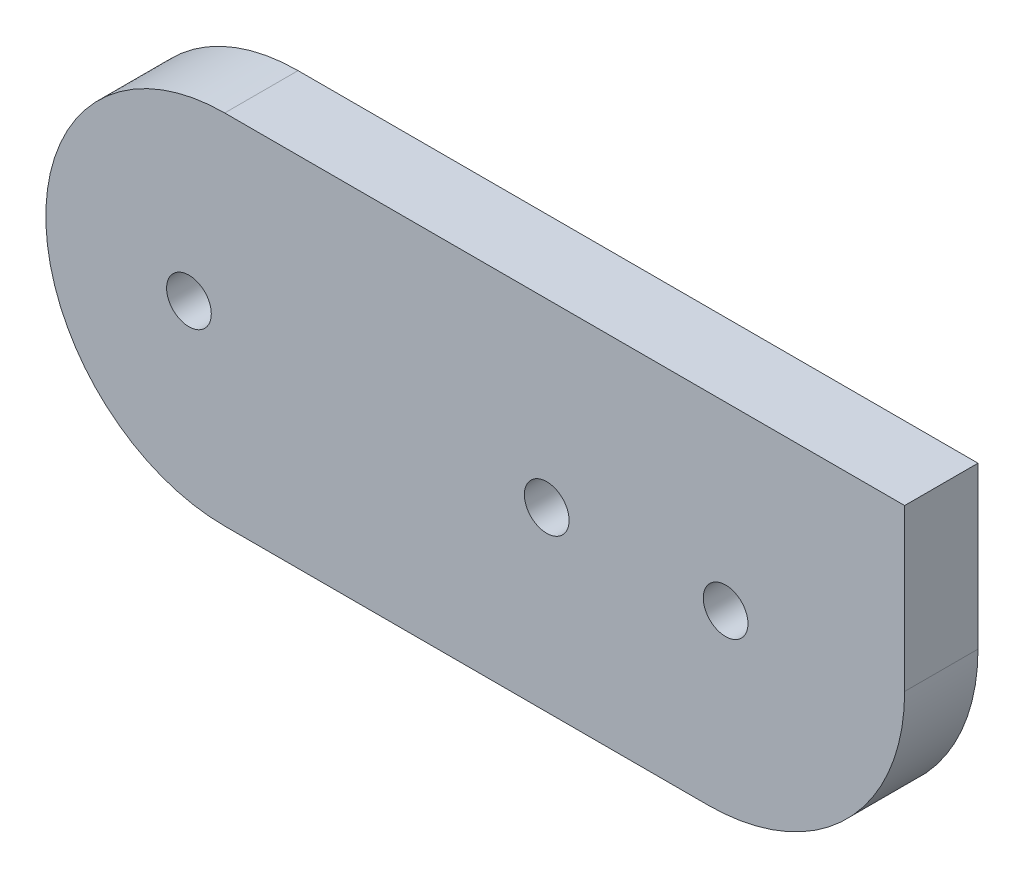
SolidWorks part; units mm, degrees
material "ABS generico"
ref_plane "Piano frontale" through (0, 0, 0) normal (0, 0, 1) x (1, 0, 0)
ref_plane "Piano superiore" through (0, 0, 0) normal (0, 1, 0) x (1, 0, 0)
ref_plane "Piano destro" through (0, 0, 0) normal (1, 0, 0) x (0, 0, -1)
sketch "Schizzo1" plane through (0, 0, 0) normal (0, 0, 1) x (1, 0, 0)
  line L0 (-12, 0) -> (-12, 8)
  line L1 (0, -12) -> (38.0086, -12)
  line L2 (38.0086, -12) -> (38.0086, 8)
  line L3 (38.0086, 8) -> (23.9979, 8)
  line L4 (23.9979, 8) -> (-12, 8)
  arc A0 (-12, 0) -> (0, -12) centre (0, 0) ccw
extrude "Estrusione-Estrusione1" add sketch "Schizzo1" along normal blind 4.1
sketch "Schizzo2" plane through (0, 0, 4.1) normal (0, 0, 1) x (1, 0, 0)
  circle A0 centre (-2, -2.1) radius 1.25
  circle A1 centre (28, -2.1) radius 1.25
  circle A2 centre (18, -2.1) radius 1.25
  dimension "D2" = 2.5
  dimension "D1" = 30
  dimension "D3" = 20
extrude "Taglio-Estrusione1" cut sketch "Schizzo2" against normal blind 4.1
fillet "Raccordo1" radius 10 1 edges at (-12, 8, 2.05)
fillet "Raccordo2" radius 11 1 edges at (38.0086, -12, 2.05)
